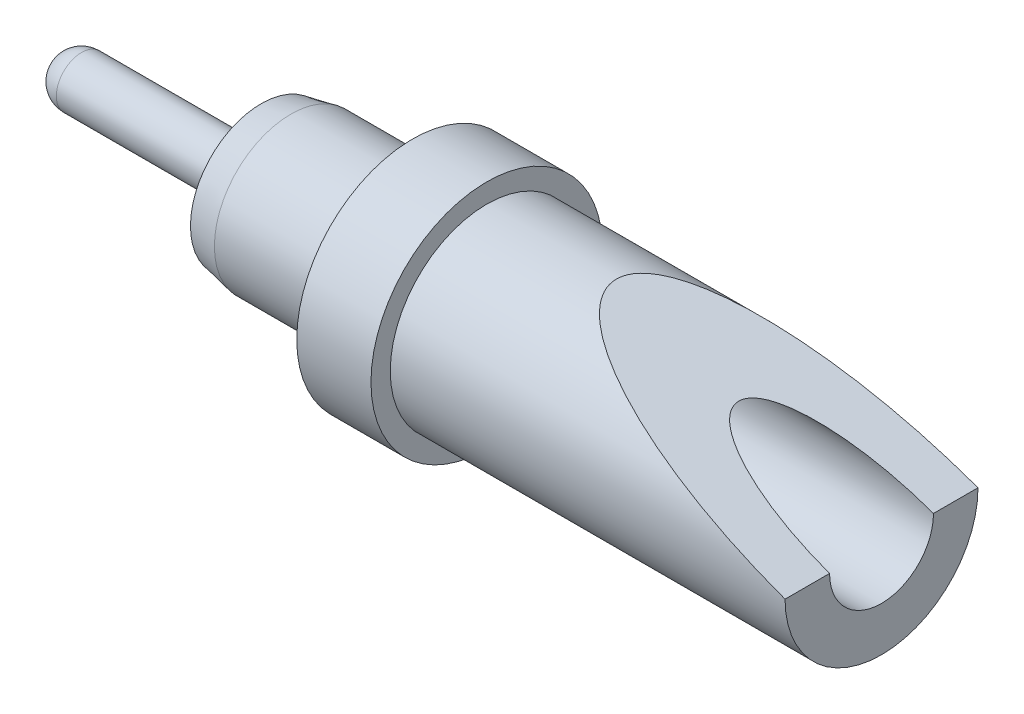
SolidWorks part; units mm, degrees
material "Brass Alloy 385"
ref_plane "Front Plane" through (0, 0, 0) normal (0, 0, 1) x (1, 0, 0)
ref_plane "Top Plane" through (0, 0, 0) normal (0, 1, 0) x (1, 0, 0)
ref_plane "Right Plane" through (0, 0, 0) normal (1, 0, 0) x (0, 0, -1)
sketch "Sketch1" plane through (0, 0, 0) normal (0, 0, 1) x (1, 0, 0)
  line L0 (0.2159, 0.2159) -> (1.6764, 0.2159)
  line L1 (0, 0) -> (7.0612, 0)
  line L2 (3.048, 0.654) -> (3.048, 0.9906)
  line L3 (3.048, 0.9906) -> (3.683, 0.9906)
  line L4 (7.0612, 0.8255) -> (7.0612, 0)
  line L5 (2.0066, 0.654) -> (3.048, 0.654)
  line L6 (0, 0) -> (7.0612, 0) construction
  line L7 (1.7526, 0.2921) -> (1.7526, 0.6047)
  line L8 (0, 0) -> (7.0612, 0) construction
  line L9 (3.683, 0.9906) -> (3.683, 0.8255)
  line L10 (1.7526, 0.6047) -> (2.0066, 0.654)
  line L11 (3.683, 0.8255) -> (7.0612, 0.8255)
  arc A0 (1.6764, 0.2159) -> (1.7526, 0.2921) centre (1.6764, 0.2921) ccw
  arc A1 (0.2159, 0.2159) -> (0, 0) centre (0.2159, 0) ccw
  dimension "M" = 1.7526
  dimension "C" = 1.9812
  dimension "O" = 3.3782
revolve "RevolutionAngle1" add sketch "Sketch1" angle 360 about L8
hole_wizard "Hole1" positions "3DSketch1" profile "Sketch2" legacy
sketch3d "3DSketch1"
  line L0 (7.0612, 0, 0) -> (3.683, 0, 0) construction
  point P0 (7.0612, 0, 0)
sketch "Sketch2" plane through (7.0612, 0, 0) normal (0, 1, 0) x (0, 0, -1)
  line L0 (0, 0) -> (0, 4.8391)
  line L1 (0, 4.8391) -> (0.4445, 4.572)
  line L2 (0.4445, 4.572) -> (0.4445, 0)
  line L4 (0.4445, 0) -> (0, 0)
  line L6 (0, 4.8391) -> (-0.4445, 4.572) construction
  line L7 (0, -4.2442) -> (0, 117.3081) construction
  dimension "A" = 0.889
  dimension "N" = 4.572
  dimension "Drill Angle" = 118
sketch "Sketch3" plane through (0, 0, 0) normal (0, 0, 1) x (1, 0, 0)
  line L0 (3.683, -0.8255) -> (7.0612, -0.8255) construction
  line L1 (7.0612, 0.8255) -> (7.0612, 0)
  line L2 (7.0612, -0.8255) -> (7.0612, 0.8255) construction
  line L3 (7.0612, 0.8255) -> (3.683, 0.8255) construction
  line L4 (7.0612, 0) -> (4.7932, 0.8255)
  line L5 (4.7932, 0.8255) -> (7.0612, 0.8255)
  dimension "S" = 2.268
  dimension "X" = 0.8255
  dimension "P2" = 20
extrude "Cut-Extrude1" cut sketch "Sketch3" against normal blind 0.889 and the other way blind 0.889
